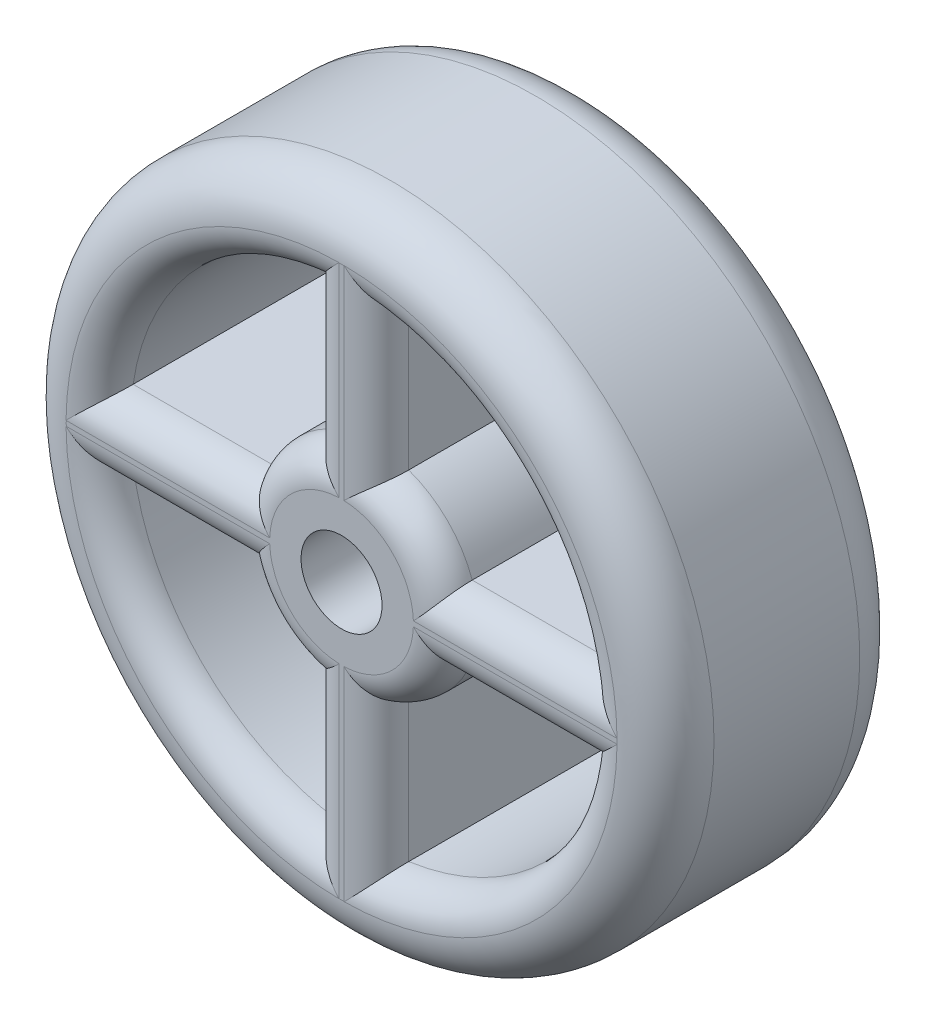
SolidWorks part; units mm, degrees
ref_plane "Front Plane" through (0, 0, 0) normal (0, 0, 1) x (1, 0, 0)
ref_plane "Top Plane" through (0, 0, 0) normal (0, 1, 0) x (1, 0, 0)
ref_plane "Right Plane" through (0, 0, 0) normal (1, 0, 0) x (0, 0, -1)
sketch "Sketch2" plane through (0, 0, 0) normal (0, 0, 1) x (1, 0, 0)
  line L12 (-2.1463, 6.0707) -> (-2.1463, 14.8701)
  line L13 (2.1463, 6.0707) -> (2.1463, 14.8701)
  line L14 (6.0707, 2.1463) -> (14.8701, 2.1463)
  line L16 (6.0647, -2.1631) -> (14.8676, -2.1631)
  line L17 (2.1463, -6.0707) -> (2.1463, -14.8701)
  line L19 (-2.1463, -6.0707) -> (-2.1463, -14.8701)
  line L20 (-6.0647, -2.1631) -> (-14.8676, -2.1631)
  line L22 (-6.0707, 2.1463) -> (-14.8701, 2.1463)
  circle A2 centre (0, 0) radius 2.5
  arc A3 (-2.1463, 6.0707) -> (-6.0707, 2.1463) centre (0, 0) ccw
  arc A4 (-2.1463, 14.8701) -> (-14.8701, 2.1463) centre (0, 0) ccw
  circle A5 centre (0, 0) radius 7.5
  circle A6 centre (0, 0) radius 20
  arc A7 (-6.0647, -2.1631) -> (-2.1463, -6.0707) centre (0, 0) ccw
  arc A8 (6.0707, 2.1463) -> (2.1463, 6.0707) centre (0, 0) ccw
  arc A9 (-14.8676, -2.1631) -> (-2.1463, -14.8701) centre (0, 0) ccw
  arc A10 (2.1463, -6.0707) -> (6.0647, -2.1631) centre (0, 0) ccw
  arc A11 (2.1463, -14.8701) -> (14.8676, -2.1631) centre (0, 0) ccw
  arc A12 (14.8701, 2.1463) -> (2.1463, 14.8701) centre (0, 0) ccw
  dimension "D1" = 5
  dimension "D2" = 40
  dimension "D3" = 15
extrude "Boss-Extrude1" add sketch "Sketch2" along normal blind 15 contours A6 A5 | A5 A12 L14 A8 L13 A11 L17 A10 L16 A9 L20 A7 L19 A2 A4 L12 A3 L22 region at (-1.9342, 6.6285, 0) region at (-19.4343, 0, 0)
sketch "Sketch3" plane through (0, 0, 15) normal (0, 0, 1) x (1, 0, 0)
  circle A0 centre (0, 0) radius 2.4167
extrude "Boss-Extrude2" add sketch "Sketch3" against normal blind 15 separate body
fillet "Fillet2" radius 2 16 edges at (-10.4704, 2.1463, 15) (-4.553, 4.553, 15) (-2.1463, 10.4704, 15) (-10.6237, 10.6237, 15) (-2.1463, -10.4704, 15) (-4.5467, -4.5593, 15) (-10.4662, -2.1631, 15) (-10.6177, -10.6297, 15) (2.1463, 10.4704, 15) (4.553, 4.553, 15) (10.4704, 2.1463, 15) (10.6237, 10.6237, 15) (10.4662, -2.1631, 15) (4.5467, -4.5593, 15) (2.1463, -10.4704, 15) (10.6177, -10.6297, 15)
fillet "Fillet3" radius 3 2 edges at (20, 0, 15) (20, 0, 0)
sketch "Sketch4" plane through (0, 0, 15) normal (0, 0, 1) x (1, 0, 0)
  circle A0 centre (0, 0) radius 2.4681
extrude "Cut-Extrude1" cut sketch "Sketch4" against normal blind 7.5
sketch "Sketch5" plane through (0, 0, 7.5) normal (0, 0, 1) x (1, 0, 0)
  circle A0 centre (0, 0) radius 2.5
extrude "Cut-Extrude2" cut sketch "Sketch5" against normal blind 10
